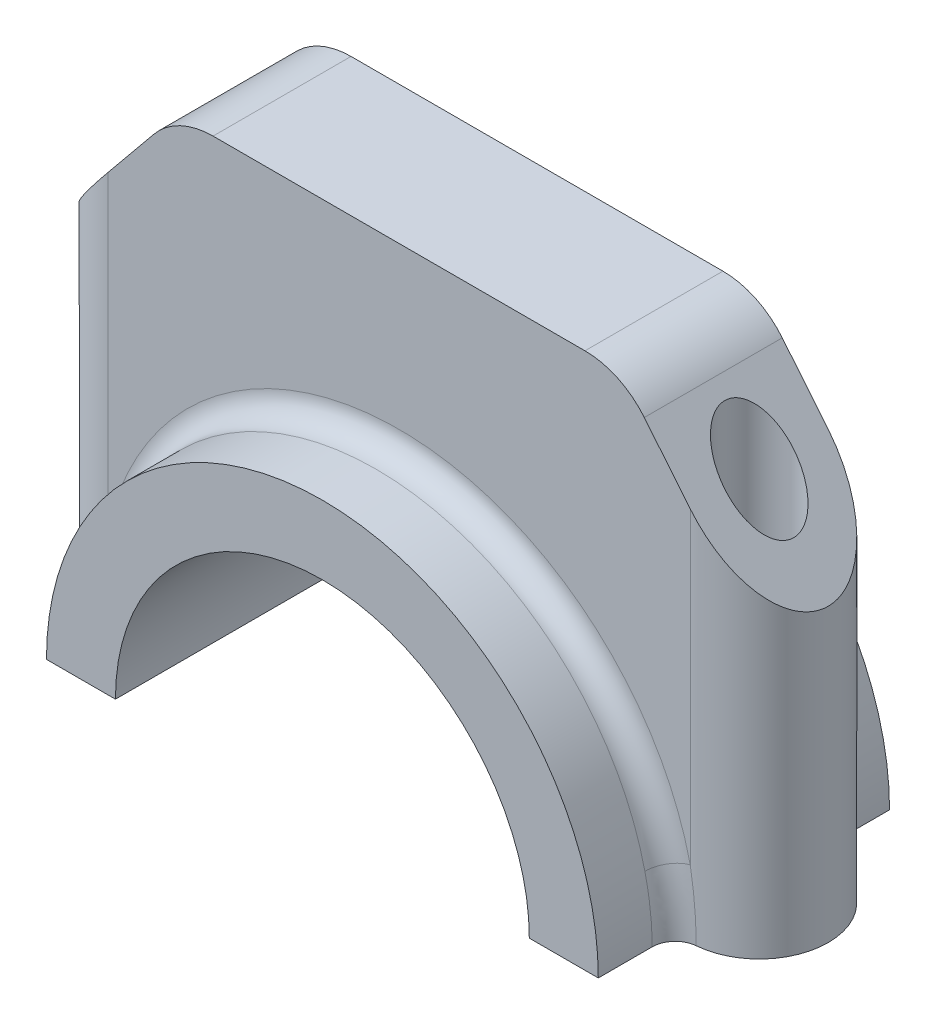
SolidWorks part; units mm, degrees
ref_plane "Front Plane" through (0, 0, 0) normal (0, 0, 1) x (1, 0, 0)
ref_plane "Top Plane" through (0, 0, 0) normal (0, 1, 0) x (1, 0, 0)
ref_plane "Right Plane" through (0, 0, 0) normal (1, 0, 0) x (0, 0, -1)
sketch "Sketch1" plane through (0, 0, 0) normal (0, 1, 0) x (1, 0, 0)
  line L0 (0, 0) -> (-76, 0) construction
  line L2 (0, -9) -> (-76, -9)
  line L3 (0, 9) -> (-76, 9)
  arc A0 (0, -9) -> (0, 9) centre (0, 0) ccw
  arc A1 (-76, 9) -> (-76, -9) centre (-76, 0) ccw
  circle A2 centre (-76, 0) radius 4.5
  circle A3 centre (0, 0) radius 4.5
  point P5 (-38, 0)
extrude "Boss-Extrude1" add sketch "Sketch1" along normal blind 60
sketch "Sketch3" plane through (0, 0, 9) normal (0, 0, 1) x (1, 0, 0)
  line L0 (-85, 60) -> (-85, 38)
  line L1 (-85, 60) -> (-85, 0) construction
  line L4 (-76, 60) -> (0, 60) construction
  line L5 (-67, 60) -> (-85, 38)
  line L6 (-85, 60) -> (-67, 60)
  line L7 (-38, 60) -> (-38, 55.9825)
  line L8 (9, 60) -> (-9, 60)
  line L9 (-9, 60) -> (9, 38)
  line L10 (9, 60) -> (9, 38)
  line M3 (0, 0) -> (0, 60)
  line M4 (0, 60) -> (-76, 60)
  line M5 (-76, 60) -> (-76, 0)
extrude "Cut-Extrude1" cut sketch "Sketch3" against normal through all contours L10 L8 L9 M3 | L9 M4 M3 | L6 L0 L5 M5 | L5 M4 M5 region at (-81, 51.4444, 9) region at (-3, 56.3333, 9) region at (-73, 56.3333, 9) region at (5, 51.4444, 9)
sketch "Sketch5" plane through (0, 0, 9) normal (0, 0, 1) x (1, 0, 0)
  line L0 (-76, 0) -> (0, 0) construction
  line L1 (-65, 0) -> (-74, 0)
  line L2 (-2, 0) -> (-11, 0)
  line L3 (-65, 0) -> (-11, 0)
  arc A0 (-2, 0) -> (-74, 0) centre (-38, 0) ccw
  arc A1 (-11, 0) -> (-65, 0) centre (-38, 0) ccw
  line M6 (-76, 0) -> (0, 0)
extrude "Cut-Extrude2" cut sketch "Sketch5" against normal through all contours A1 M6 region at (-38, 11.4592, 9)
extrude "Boss-Extrude2" add sketch "Sketch5<3>" along normal blind 10 and the other way blind 28 contours A1 A0 M6 region at (-69.5, 0.805, 9)
sketch "Sketch5<3>" plane through (0, 0, 9) normal (0, 0, 1) x (1, 0, 0) same geometry as "Sketch5"
sketch "Sketch6" plane through (0, 0, 0) normal (0, -1, 0) x (1, 0, 0)
  circle A0 centre (-76, 0) radius 4.5
  circle A1 centre (0, 0) radius 4.5
extrude "Cut-Extrude3" cut sketch "Sketch6" against normal through all
fillet "Fillet1" radius 3 2 edges at (-38, 36, -9) (-38, 36, 9)
fillet "Fillet2" radius 10 2 edges at (-9, 60, 0) (-67, 60, 0)
